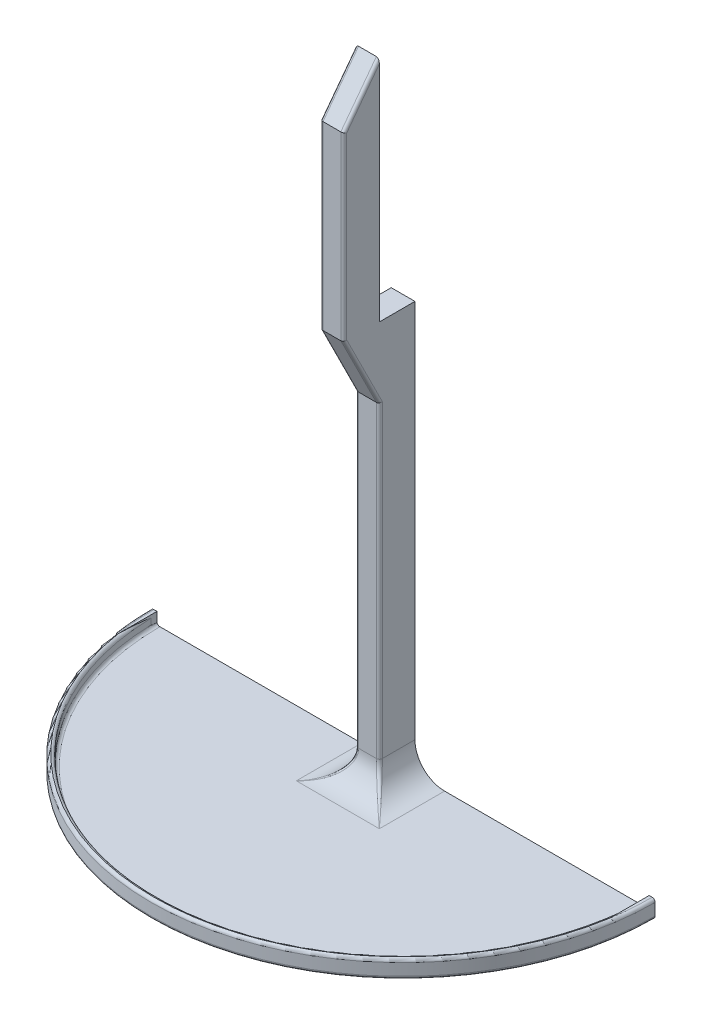
SolidWorks part; units mm, degrees
ref_plane "Front Plane" through (0, 0, 0) normal (0, 0, 1) x (1, 0, 0)
ref_plane "Top Plane" through (0, 0, 0) normal (0, 1, 0) x (1, 0, 0)
ref_plane "Right Plane" through (0, 0, 0) normal (1, 0, 0) x (0, 0, -1)
sketch "Sketch1" plane through (0, 0, 0) normal (0, 1, 0) x (1, 0, 0)
  line L0 (-42.5, 0) -> (42.5, 0)
  line L1 (-41.488, -1) -> (41.488, -1)
  arc A0 (-42.5, 0) -> (42.5, 0) centre (0, 0) ccw
  arc A1 (-41.488, -1) -> (41.488, -1) centre (0, 0) ccw
  point P4 (0, 0)
  dimension "D1" = 85
  dimension "D2" = 1
extrude "Boss-Extrude1" add sketch "Sketch1" along normal blind 3 contours L0 A0 A1 L1 region at (0, 0, 0.9503)
extrude "Boss-Extrude2" add sketch "Sketch1<4>" along normal blind 1 contours L1 A1 region at (0, 0, 18.1548)
sketch "Sketch1<4>" plane through (0, 0, 0) normal (0, 1, 0) x (1, 0, 0) same geometry as "Sketch1"
sketch "Sketch3" plane through (0, 3, 0) normal (0, 1, 0) x (1, 0, 0)
  line L0 (2, 0) -> (-2, 0)
  line L1 (2, 0) -> (2, -6)
  line L2 (-2, 0) -> (-2, -6)
  line L3 (2, -6) -> (-2, -6)
  line L4 (-42.5, 0) -> (42.5, 0) construction
  line L5 (2, -1) -> (-2, -1)
  line L6 (-41.488, -1) -> (41.488, -1) construction
  point P6 (0, 0)
  point P7 (0, 0)
  point P8 (0, 0)
  line M6 (-41.488, -1) -> (41.488, -1)
  line M7 (42.5, 0) -> (-42.5, 0)
  dimension "D1" = 6
  dimension "D2" = 4
extrude "Boss-Extrude3" add sketch "Sketch3" against normal up to surface (2 mm away) contours L3 L1 L2 M6 region at (0, 3, 3.5) up to face at (0, 1, 21.25)
extrude "Boss-Extrude4" add sketch "Sketch3<3>" along normal blind 67 contours L3 L1 L2 M6 | L2 L1 M7 M6 region at (0, 3, 0.5) region at (0, 3, 3.5)
sketch "Sketch3<3>" plane through (0, 3, 0) normal (0, 1, 0) x (1, 0, 0) same geometry as "Sketch3"
sketch "Sketch4" plane through (0, 3, 0) normal (0, 1, 0) x (1, 0, 0)
  line L1 (41.488, -1) -> (2, -1)
  line L2 (41.488, -1) -> (41.488, 0)
  line L3 (41.488, 0) -> (2, 0)
  line L4 (2, -1) -> (2, 0)
  line L5 (-41.488, -1) -> (-2, -1)
  line L6 (-41.488, -1) -> (-41.488, 0)
  line L7 (-41.488, 0) -> (-2, 0)
  line L8 (-2, -1) -> (-2, 0)
extrude "Cut-Extrude1" cut sketch "Sketch4" against normal up to surface (2 mm away) up to face at (0, 1, 9.4167)
sketch "Sketch5" plane through (0, 70, 0) normal (0, 1, 0) x (1, 0, 0)
  line L0 (-2, -6) -> (2, -6)
  line L1 (-2, -6) -> (-2, -12)
  line L2 (2, -6) -> (2, -12)
  line L3 (-2, -12) -> (2, -12)
  dimension "D1" = 6
extrude "Boss-Extrude5" add sketch "Sketch5" along normal blind 38.5 separate body
sketch "Sketch6" plane through (2, 0, 0) normal (1, 0, 0) x (0, 0, -1)
  line L0 (-12, 70) -> (-6, 70)
  line L1 (-6, 70) -> (-6, 58)
  line L2 (-6, 1) -> (-6, 70) construction
  line L3 (-6, 58) -> (-12, 70)
  dimension "D1" = 12
extrude "Boss-Extrude6" add sketch "Sketch6" against normal up to surface (4 mm away) up to face at (-2, 89.25, 9)
sketch "Sketch7" plane through (2, 0, 0) normal (1, 0, 0) x (0, 0, -1)
  line L0 (-6, 108.5) -> (-12, 108.5)
  line L1 (-12, 108.5) -> (-12, 100.5)
  line L2 (-12, 108.5) -> (-12, 70) construction
  line L3 (-12, 100.5) -> (-6, 108.5)
  dimension "D1" = 8
extrude "Cut-Extrude2" cut sketch "Sketch7" against normal through all
fillet "Fillet1" radius 0.5 4 edges at (0, 1, 41.5) (0, 0, 42.5) (0, 3, 41.5) (0, 3, 42.5)
fillet "Fillet2" radius 5 3 edges at (2, 1, 3) (-2, 1, 3) (0, 1, 6)
fillet "Fillet3" radius 0.5 10 edges at (-3.4645, 2.4645, 7.4645) (3.4645, 2.4645, 7.4645) (2, 104.5, 9) (-2, 104.5, 9) (-2, 85.25, 12) (2, 85.25, 12) (2, 64, 9) (-2, 64, 9) (-2, 32, 6) (2, 32, 6)
